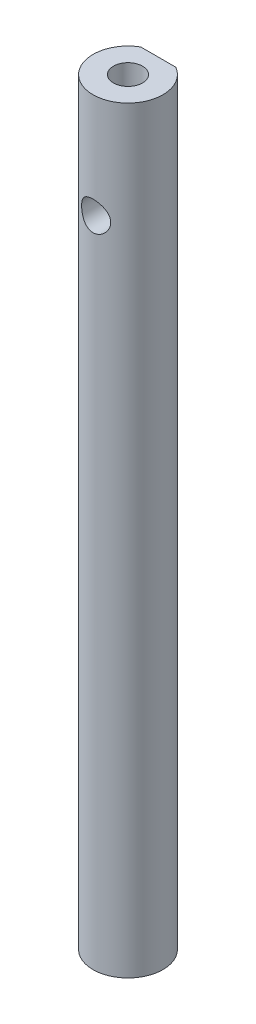
SolidWorks part; units mm, degrees
ref_plane "前视基准面" through (0, 0, 0) normal (0, 0, 1) x (1, 0, 0)
ref_plane "上视基准面" through (0, 0, 0) normal (0, 1, 0) x (1, 0, 0)
ref_plane "右视基准面" through (0, 0, 0) normal (1, 0, 0) x (0, 0, -1)
sketch "草图1" plane through (0, 0, 0) normal (0, 1, 0) x (1, 0, 0)
  circle A0 centre (0, 0) radius 3
extrude "凸台-拉伸2" add sketch "草图1" along normal blind 65
sketch "草图2" plane through (0, 65, 0) normal (0, 1, 0) x (1, 0, 0)
  line L0 (-1.5, 2.5981) -> (1.5, 2.5981)
  line L1 (-1.5, 2.5981) -> (-1.5, 7.3514)
  line L2 (1.5, 2.5981) -> (1.5, 7.3514)
  line L3 (-1.5, 7.3514) -> (1.5, 7.3514)
  circle A0 centre (0, 0) radius 3 construction
  dimension "D1" = 3
extrude "切除-拉伸1" cut sketch "草图2" against normal blind 12
sketch "草图3" plane through (0, 0, -2.5981) normal (0, 0, -1) x (-1, 0, 0)
  line L0 (0, 65) -> (0, 0) construction
  line L1 (1.5, 65) -> (-1.5, 65) construction
  point P5 (0, 56)
  dimension "D1" = 9
hole_wizard "M3 螺纹孔1" positions "草图4" profile "草图5" tap size "M3" standard "GB" end condition through all
sketch "草图4" plane through (0, 0, -2.5981) normal (0, 0, -1) x (-1, 0, 0)
  point P0 (0, 56)
sketch "草图5" plane through (0, 56, -2.5981) normal (1, 0, 0) x (0, 1, 0)
  line L0 (0, 0) -> (0, 5.5981)
  line L1 (0, 5.5981) -> (1.25, 5.5981)
  line L2 (1.25, 5.5981) -> (1.25, 0)
  line L5 (1.25, 0) -> (0, 0)
  line L11 (0, -6.35) -> (0, 107.95) construction
  dimension "通孔螺纹孔钻头直径" = 2.5
  dimension "通孔螺纹孔钻头深度" = 5.5981
cosmetic thread "孔螺蚊线1" parameters "D2"=3
hole_wizard "M3 螺纹孔2" positions "草图6" profile "草图7" tap size "M3" standard "GB"
sketch "草图6" plane through (0, 65, 0) normal (0, 1, 0) x (1, 0, 0)
  point P0 (0, 0)
sketch "草图7" plane through (0, 65, 0) normal (1, 0, 0) x (0, 0, 1)
  line L0 (0, 0) -> (0, 6.7511)
  line L1 (0, 6.7511) -> (1.25, 6)
  line L2 (1.25, 6) -> (1.25, 0)
  line L5 (1.25, 0) -> (0, 0)
  line L10 (0, 6.7511) -> (-1.25, 6) construction
  line L11 (0, -6.35) -> (0, 107.95) construction
  dimension "螺纹孔钻头直径" = 2.5
  dimension "螺纹孔钻头深度" = 6
  dimension "导头角度" = 118
cosmetic thread "孔螺蚊线2" parameters "D1"=6, "D2"=3
